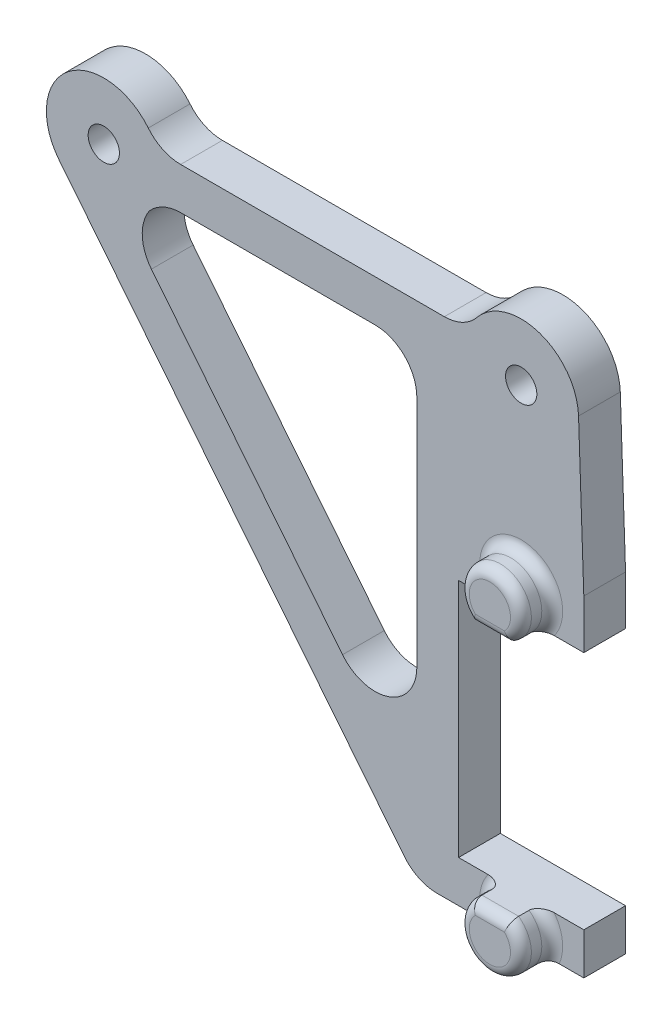
SolidWorks part; units mm, degrees
ref_plane "Front Plane" through (0, 0, 0) normal (0, 0, 1) x (1, 0, 0)
ref_plane "Top Plane" through (0, 0, 0) normal (0, 1, 0) x (1, 0, 0)
ref_plane "Right Plane" through (0, 0, 0) normal (1, 0, 0) x (0, 0, -1)
sketch "screw holes" plane through (0, 0, 0) normal (0, 0, 1) x (1, 0, 0)
  line L0 (0, 0) -> (-40, 0) construction
  circle A0 centre (0, 0) radius 1.5
  circle A1 centre (-40, 0) radius 1.5
  dimension "D1" = 3
  dimension "D2" = 40
sketch "bottom of holder" plane through (0, 0, 0) normal (0, 0, 1) x (1, 0, 0)
  line L0 (0, 0) -> (0, -14.5) construction
  line L1 (0, -14.5) -> (-8.6529, -14.5)
  dimension "D1" = 14.5
sketch "servo mount" plane through (0, 0, 0) normal (0, 0, 1) x (1, 0, 0)
  line L0 (0, -14.5) -> (0, -46.9) construction
  line L1 (6, -46.9) -> (-6, -46.9)
  line L2 (-6, -46.9) -> (-6, -14.5)
  line L3 (0, -14.5) -> (-8.6529, -14.5) construction
  line L4 (-6, -14.5) -> (6, -14.5)
  line L5 (6, -14.5) -> (6, -46.9)
  dimension "D1" = 32.4
  dimension "D2" = 12
sketch "servo body" plane through (0, 0, 0) normal (0, 0, 1) x (1, 0, 0)
  line L0 (0, -14.5) -> (0, -46.9) construction
  line L1 (-6, -42.2) -> (6, -42.2)
  line L2 (-6, -42.2) -> (-6, -19.2)
  line L3 (-6, -19.2) -> (6, -19.2)
  line L4 (6, -42.2) -> (6, -19.2)
  line L5 (-6, -42.2) -> (6, -19.2) construction
  line L6 (-6, -19.2) -> (6, -42.2) construction
  line L7 (6, -14.5) -> (6, -46.9) construction
  point P0 (0, -30.7)
  dimension "D1" = 23
sketch "servo screw holes" plane through (0, 0, 0) normal (0, 0, 1) x (1, 0, 0)
  line L0 (0, -17.775) -> (0, -43.625)
  circle A0 centre (0, -16.8) radius 0.975
  circle A1 centre (0, -44.6) radius 0.975
  point P5 (0, -30.7)
  dimension "D2" = 1.95
  dimension "D1" = 25.85
sketch "mount body" plane through (0, 0, 0) normal (0, 0, 1) x (1, 0, 0)
  line L0 (-10, -15.2) -> (-10, -39.8064)
  line L1 (-10, -46.2) -> (-2.5081, -46.2)
  line L4 (-6, -42.2) -> (6, -42.2)
  line L5 (6, -42.2) -> (6, -19.2)
  line L6 (6, -19.2) -> (-6, -19.2)
  line L7 (-6, -19.2) -> (-6, -42.2)
  line L8 (-6, -42.2) -> (6, -42.2) construction
  line L9 (6, -42.2) -> (6, -19.2) construction
  line L10 (6, -19.2) -> (-6, -19.2) construction
  line L11 (-6, -19.2) -> (-6, -42.2) construction
  line L12 (-34.8765, 2) -> (-5.1235, 2)
  line L13 (26.125, 0) -> (-26.125, 0) construction
  line L14 (-34.8765, -2) -> (-10, -2)
  line L16 (-10, -15.2) -> (-10, -2)
  line L17 (10, -15.2) -> (-10, -15.2) construction
  line L18 (2.5081, -46.2) -> (6, -46.2)
  line L19 (-10, -46.2) -> (10, -46.2) construction
  line L22 (6, -19.2) -> (-6, -19.2)
  line L23 (-6, -19.2) -> (-6, -42.2)
  line L24 (-6, -42.2) -> (6, -42.2)
  line L26 (10, -46.2) -> (10, -15.2) construction
  line L27 (6, -42.2) -> (6, -46.2)
  line L28 (6, -19.2) -> (6, -14.5)
  line L29 (6, -14.5) -> (5.4968, 0.1883)
  line L30 (-44.2907, -3.4409) -> (-10, -46.2)
  line L31 (-37.8597, -5.0665) -> (-10, -39.8064)
  line L32 (-10, -15.2) -> (-10, -46.2) construction
  arc A0 (-34.8765, 2) -> (-44.2907, -3.4409) centre (-40, 0) ccw
  circle A1 centre (-40, 0) radius 1.5
  circle A2 centre (-40, 0) radius 1.5 construction
  circle A3 centre (0, 0) radius 1.5
  circle A4 centre (0, 0) radius 1.5 construction
  arc A5 (5.4968, 0.1883) -> (-5.1235, 2) centre (0, 0) ccw
  circle A6 centre (-40, 0) radius 5.5 construction
  circle A7 centre (0, 0) radius 5.5 construction
  arc A8 (-37.8597, -5.0665) -> (-34.8765, -2) centre (-40, 0) ccw
  circle A16 centre (0, -44.6) radius 2.975
  arc A17 (-2.5081, -46.2) -> (2.5081, -46.2) centre (0, -44.6) ccw
  dimension "D6" = 4
  dimension "D7" = 2
  dimension "D8" = 4
  dimension "D1" = 0
  dimension "D2" = 0
  dimension "D3" = 0
  dimension "D4" = 4
  dimension "D5" = 4
extrude "Boss-Extrude1" add sketch "mount body" along normal blind 4
fillet "Fillet2" radius 4 7 edges at (-10, -39.8064, 2) (-10, -2, 2) (-5.1235, 2, 2) (-34.8765, 2, 2) (-37.8597, -5.0665, 2) (-34.8765, -2, 2) (-10, -46.2, 2)
sketch "Sketch11" plane through (0, 0, 0) normal (0, 0, 1) x (1, 0, 0)
  line L0 (-6, -19.2) -> (6, -19.2) construction
  line L1 (-1.758, -19.2) -> (1.758, -19.2)
  line L2 (-6, -42.2) -> (6, -42.2) construction
  line L3 (-1.758, -42.2) -> (1.758, -42.2)
  circle A5 centre (0, -16.8) radius 2.975
  arc A6 (1.758, -19.2) -> (-1.758, -19.2) centre (0, -16.8) ccw
  circle A8 centre (0, -44.6) radius 2.975
  arc A9 (-1.758, -42.2) -> (1.758, -42.2) centre (0, -44.6) ccw
  dimension "D1" = 2
  dimension "D2" = 2
extrude "Boss-Extrude3" add sketch "Sketch11" along normal blind 7
sketch "Sketch12" plane through (0, 0, 0) normal (0, 0, 1) x (1, 0, 0)
  line L0 (0, 0) -> (-40, 0) construction
  circle A0 centre (0, 0) radius 1.5
  circle A1 centre (-40, 0) radius 1.5
  dimension "D1" = 3
  dimension "D2" = 40
extrude "Cut-Extrude3" cut sketch "Sketch12" along normal through all
sketch "Sketch13" plane through (0, 0, 0) normal (0, 0, 1) x (1, 0, 0)
  line L0 (0, -17.775) -> (0, -43.625) construction
  circle A0 centre (0, -16.8) radius 0.975
  circle A1 centre (0, -44.6) radius 0.975
  dimension "D2" = 1.95
  dimension "D1" = 25.85
extrude "Cut-Extrude4" cut sketch "Sketch13" along normal blind 5.5
fillet "Fillet3" radius 1 9 edges at (0, -42.2, 7) (0, -47.575, 7) (0, -19.2, 7) (0, -13.825, 7) (-2.5081, -46.2, 2) (2.5081, -46.2, 2) (2.924, -44.0517, 4) (-2.924, -44.0517, 4) (0, -13.825, 4)
